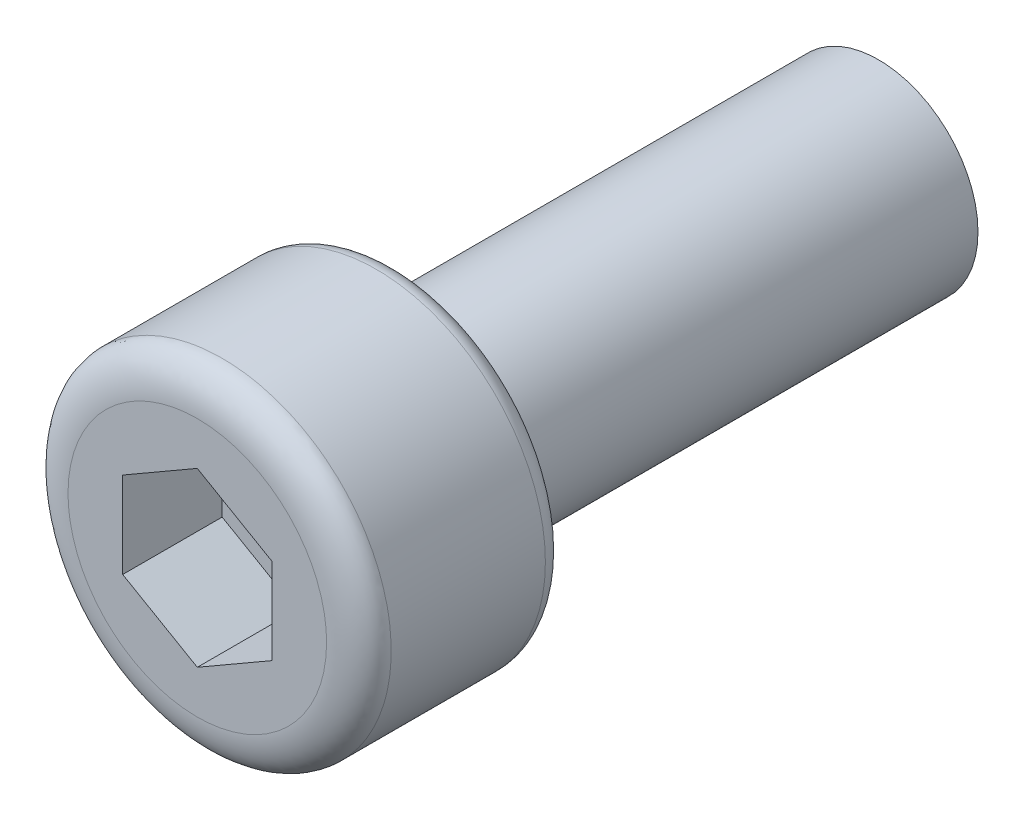
SolidWorks part; units mm, degrees
ref_plane "前视基准面" through (0, 0, 0) normal (0, 0, 1) x (1, 0, 0)
ref_plane "上视基准面" through (0, 0, 0) normal (0, 1, 0) x (1, 0, 0)
ref_plane "右视基准面" through (0, 0, 0) normal (1, 0, 0) x (0, 0, -1)
sketch "草图2" plane through (0, 0, 0) normal (1, 0, 0) x (0, 0, -1)
  line L0 (-7, 0) -> (-7, 3.4)
  line L1 (-7, 3.4) -> (-3, 3.4)
  line L2 (-3, 3.4) -> (-3, 2)
  line L3 (-3, 2) -> (7, 2)
  line L4 (7, 2) -> (7, 0)
  line L5 (7, 0) -> (-7, 0)
  dimension "D1" = 10
  dimension "D2" = 3.4
  dimension "D3" = 2
  dimension "D4" = 4
revolve "旋转1" add sketch "草图2" angle 360 about L5
chamfer "倒角1" distance 0.3 angle 60 1 edges at (-2, 0, -7) first distance on face at (-2, 0, 3)
fillet "圆角1" radius 0.4 1 edges at (-3.4, 0, 3)
fillet "圆角2" radius 0.8 1 edges at (-3.4, 0, 7) second distance 0.5 first distance on face at (-3.4, 0, 7)
sketch "草图3" plane through (0, 0, 7) normal (0, 0, 1) x (1, 0, 0)
  line L1 (0, 1.7321) -> (-1.5, 0.866)
  line L2 (-1.5, 0.866) -> (-1.5, -0.866)
  line L3 (-1.5, -0.866) -> (0, -1.7321)
  line L4 (0, -1.7321) -> (1.5, -0.866)
  line L5 (1.5, -0.866) -> (1.5, 0.866)
  line L6 (1.5, 0.866) -> (0, 1.7321)
  circle A0 centre (0, 0) radius 1.5 construction
  dimension "D1" = 3
extrude "切除-拉伸1" cut sketch "草图3" against normal blind 2
